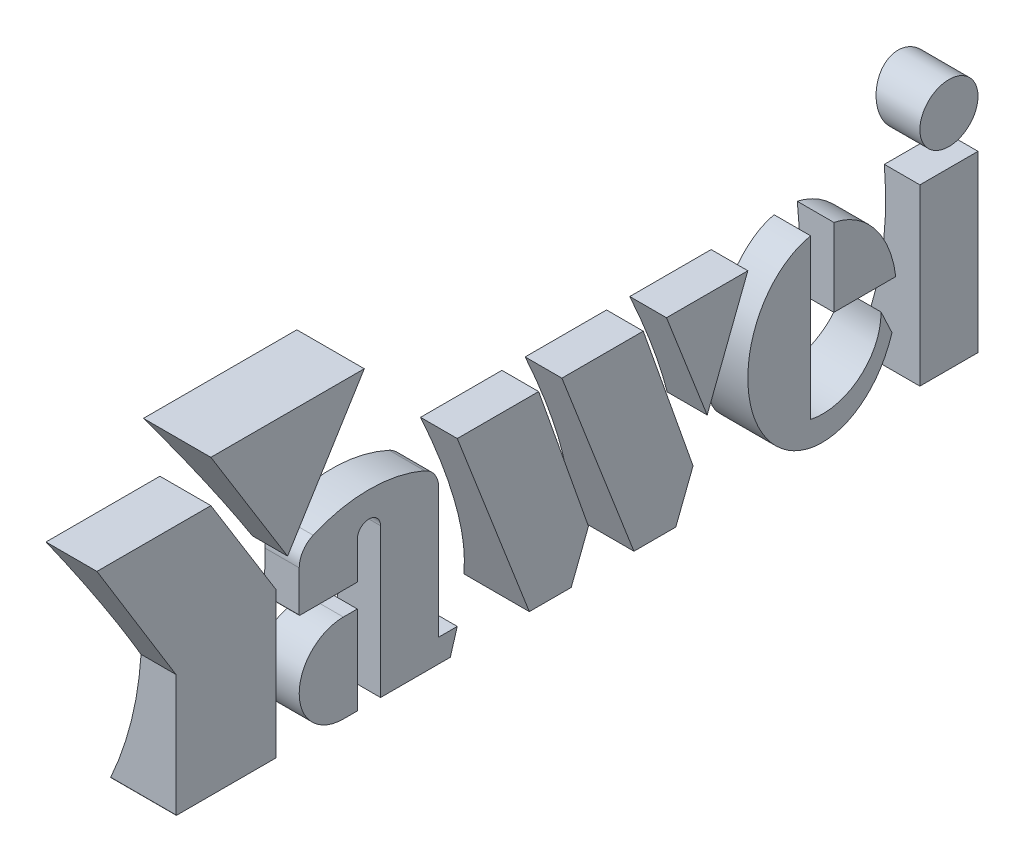
SolidWorks part; units mm, degrees
ref_plane "前视基准面" through (0, 0, 0) normal (0, 0, 1) x (1, 0, 0)
ref_plane "上视基准面" through (0, 0, 0) normal (0, 1, 0) x (1, 0, 0)
ref_plane "右视基准面" through (0, 0, 0) normal (1, 0, 0) x (0, 0, -1)
sketch "草图2" plane through (0, 0, 0) normal (1, 0, 0) x (0, 0, -1)
  line L0 (7.4295, 429.4279) -> (3.4295, 429.4279)
  line L1 (3.4295, 424.4279) -> (5.9295, 424.4279)
  line L2 (-53.0705, 450.7151) -> (-53.0705, 424.5779)
  line L3 (-31.5705, 424.4279) -> (-31.5705, 455.8075)
  line L4 (-14.0705, 443.4279) -> (-14.0705, 424.4279)
  line L5 (-9.0705, 456.4279) -> (-9.0705, 424.4279)
  line L6 (-52.9205, 424.4279) -> (-31.5705, 424.4279)
  line L7 (-9.0705, 424.4279) -> (3.4295, 424.4279)
  line L8 (-17.0705, 424.4279) -> (-14.0705, 424.4279)
  line L9 (-45.5705, 487.4279) -> (-29.0705, 460.7682)
  line L10 (-12.5705, 487.4279) -> (-45.5705, 487.4279)
  line L11 (-12.5705, 487.4279) -> (-45.5705, 487.4279)
  line L12 (-45.5705, 478.4279) -> (-31.5705, 455.8075)
  line L13 (-70.0705, 478.4279) -> (-53.0705, 450.7151)
  line L14 (-45.5705, 478.4279) -> (-70.0705, 478.4279)
  line L15 (-26.4205, 448.4279) -> (-14.0705, 448.4279)
  line L16 (-26.5705, 457.3407) -> (-26.5705, 448.5779)
  line L17 (3.4295, 457.3407) -> (3.4295, 429.4279)
  line L18 (-17.0705, 443.4279) -> (-14.0705, 443.4279)
  line L19 (-14.0705, 456.4279) -> (-14.0705, 448.4279)
  line L20 (-12.5705, 487.4279) -> (-29.0705, 460.7682)
  line L21 (106.9295, 461.9279) -> (119.4295, 461.9279)
  line L22 (119.4295, 461.9279) -> (119.4295, 424.4279)
  line L23 (119.4295, 424.4279) -> (106.9295, 424.4279)
  line L24 (106.9295, 424.4279) -> (106.9295, 461.9279)
  line L25 (58.1429, 433.9767) -> (54.4295, 424.4279)
  line L26 (35.6429, 433.9767) -> (31.9295, 424.4279)
  line L27 (29.9295, 464.4279) -> (45.4295, 424.4279)
  line L28 (5.9295, 424.4279) -> (7.4295, 429.4279)
  line L29 (7.4295, 464.4279) -> (22.9295, 424.4279)
  line L30 (54.4295, 424.4279) -> (45.4295, 424.4279)
  line L31 (31.9295, 424.4279) -> (22.9295, 424.4279)
  line L32 (47.4295, 464.4279) -> (58.1429, 433.9767)
  line L33 (52.4295, 464.4279) -> (61.1795, 441.9279)
  line L34 (52.4295, 464.4279) -> (69.9295, 464.4279)
  line L35 (24.9295, 464.4279) -> (35.6429, 433.9767)
  line L36 (7.4295, 464.4279) -> (24.9295, 464.4279)
  line L37 (29.9295, 464.4279) -> (47.4295, 464.4279)
  line L38 (69.9295, 464.4279) -> (61.1795, 441.9279)
  line L39 (88.4295, 464.1822) -> (88.4295, 447.4279)
  line L40 (83.4295, 464.1822) -> (83.4295, 429.9694)
  line L41 (98.5708, 442.43) -> (100.9175, 437.4279)
  line L42 (88.4295, 447.4279) -> (101.804, 447.4279)
  arc A0 (-17.0705, 443.4279) -> (-17.0705, 424.4279) centre (-17.0705, 433.9279) ccw
  arc A1 (-53.0705, 424.5779) -> (-52.9205, 424.4279) centre (-52.9205, 424.5779) ccw
  arc A2 (-23.5705, 461.9233) -> (-26.5705, 457.3407) centre (-21.5705, 457.3407) ccw
  arc A3 (3.4295, 457.3407) -> (0.4295, 461.9233) centre (-1.5705, 457.3407) ccw
  arc A4 (-26.5705, 448.5779) -> (-26.4205, 448.4279) centre (-26.4205, 448.5779) ccw
  arc A5 (-9.0705, 456.4279) -> (-14.0705, 456.4279) centre (-11.5705, 456.4279) ccw
  arc A6 (0.4295, 461.9233) -> (-23.5705, 461.9233) centre (-11.5705, 434.4279) ccw
  arc A7 (83.4295, 429.9694) -> (98.5708, 442.43) centre (85.9993, 442.2764) ccw
  circle A8 centre (113.1795, 472.1779) radius 6.25
  ellipse E0 centre (85.9295, 444.4279) end of major axis (85.9295, 464.4279) minor radius 16 (83.4295, 464.1822) -> (100.9175, 437.4279) ccw
  ellipse E1 centre (85.9295, 444.4279) end of major axis (85.9295, 464.4279) minor radius 16 (101.7485, 447.4279) -> (88.4295, 464.1822) ccw
extrude "凸台-拉伸1" add sketch "草图2" along normal blind 20 contours L40 E0 L41 A7 | L42 E1 L39 | L24 L23 L22 L21 | A8 | L38 L34 L33 | L37 L27 L30 L25 L32 | L36 L29 L31 L26 L35 | A3 A6 A2 L16 A4 L15 L19 A5 L5 L7 L1 L28 L0 L17 | L18 A0 L8 L4 | L2 A1 L6 L3 L12 L14 L13 region at (0, 447.0464, 7.4575) region at (0, 452.3186, 46.2215) region at (0, 433.9279, 19.516) region at (0, 443.1779, -113.1795) region at (0, 445.6168, -45.3295) region at (0, 445.6168, -22.8295) region at (0, 456.9279, -61.1795) region at (0, 454.2104, -93.8247) region at (0, 441.7714, -80.6892) region at (0, 472.1779, -113.1795)
extrude "凸台-拉伸2" add sketch "草图2<3>" along normal blind 20 separate body contours L20 L10 L9 region at (0, 478.5413, 29.0705)
sketch "草图2<3>" plane through (0, 0, 0) normal (1, 0, 0) x (0, 0, -1) same geometry as "草图2"
sketch "草图3" plane through (0, 0, -119.4295) normal (0, 0, -1) x (-1, 0, 0)
  circle A0 centre (57.4554, 453.1278) radius 75
  dimension "D1" = 150
extrude "切除-拉伸1" [suppressed] cut sketch "草图3" against normal through all
sketch "草图4" plane through (0, 0, -119.4295) normal (0, 0, -1) x (-1, 0, 0)
  circle A0 centre (62.365, 455.4875) radius 75
  dimension "D1" = 150
extrude "切除-拉伸2" cut sketch "草图4" against normal through all
